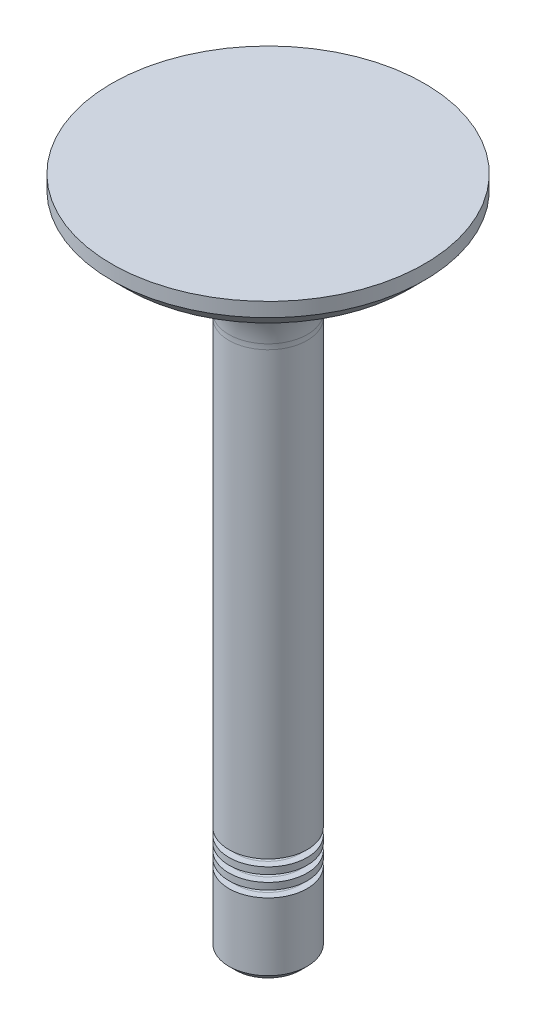
SolidWorks part; units mm, degrees
material "21-2N"
ref_plane "Front Plane" through (0, 0, 0) normal (0, 0, 1) x (1, 0, 0)
ref_plane "Top Plane" through (0, 0, 0) normal (0, 1, 0) x (1, 0, 0)
ref_plane "Right Plane" through (0, 0, 0) normal (1, 0, 0) x (0, 0, -1)
sketch "Sketch1" plane through (0, 0, 0) normal (0, 0, 1) x (1, 0, 0)
  line L0 (0, 105.7218) -> (0, 5.7218) construction
  line L1 (0, 105.7218) -> (-23.22, 105.7218)
  line L2 (-23.22, 105.7218) -> (-23.22, 103.6218)
  line L3 (-23.22, 103.6218) -> (-20.898, 101.2998)
  line L4 (0, 105.7218) -> (0, 5.7218)
  line L5 (-5.805, 87.4698) -> (-5.805, 5.7218)
  line L6 (-5.805, 5.7218) -> (0, 5.7218)
  arc A0 (-20.898, 101.2998) -> (-5.805, 87.4698) centre (-20.2665, 86.8383) cw
  dimension "D2" = 23.22
  dimension "D3" = 2.1
  dimension "D4" = 45
  dimension "D1" = 5.805
  dimension "D6" = 100
  dimension "D5" = 2.322
  dimension "D8" = 16.152
revolve "Revolve1" add sketch "Sketch1" angle 360 about L0
fillet "Fillet1" radius 10 1 edges at (-5.805, 87.4698, 0)
chamfer "Chamfer1" distance 1 angle 45 1 edges at (-5.805, 5.7218, 0)
sketch "Sketch2" plane through (0, 0, 0) normal (1, 0, 0) x (0, 0, -1)
  line L2 (-6.805, 19.7218) -> (-4.805, 19.7218)
  line L3 (-6.805, 18.7218) -> (-4.805, 18.7218)
  line L4 (0, 6.7218) -> (0, 87.9734) construction
  line L5 (5.805, 6.7218) -> (-5.805, 6.7218) construction
  line L6 (5.8358, 87.9734) -> (-5.8358, 87.9734) construction
  line L7 (-6.805, 18.7218) -> (-6.805, 19.7218)
  line L8 (-6.805, 16.7218) -> (-4.805, 16.7218)
  line L9 (-6.805, 16.7218) -> (-6.805, 17.7218)
  line L10 (-6.805, 17.7218) -> (-4.805, 17.7218)
  line L12 (-6.805, 21.7218) -> (-4.805, 21.7218)
  line L13 (-6.805, 20.7218) -> (-4.805, 20.7218)
  line L14 (-6.805, 20.7218) -> (-6.805, 21.7218)
  arc A1 (-4.805, 16.7218) -> (-4.805, 17.7218) centre (-4.805, 17.2218) ccw
  arc A2 (-4.805, 18.7218) -> (-4.805, 19.7218) centre (-4.805, 19.2218) ccw
  arc A3 (-4.805, 20.7218) -> (-4.805, 21.7218) centre (-4.805, 21.2218) ccw
  point P10 (-5.805, 17.2218)
  dimension "D1" = 10
  dimension "D2" = 1
  dimension "D3" = 3
revolve "Cut-Revolve1" cut sketch "Sketch2" angle 360 about L4
sketch "Sketch3" plane through (0, 0, 0) normal (0, 0, 1) x (1, 0, 0)
  line L0 (0, 105.7218) -> (0, -4.6075) construction
  line L1 (23.22, 105.7218) -> (-23.22, 105.7218) construction
equation "\"Valve Diameter\"= 46.44mm"
equation "\"Seat Angle Beta\"= 45deg"
equation "\"Seat Diameter\"= 41.796mm"
equation "\"Stem Diameter\"= 11.61mm"
equation "\"Seat Width\"= 2.322mm"
equation "\"Max Lift\"= 16.152mm"
equation "\"Overall Length\"= 100mm"
equation "\"Head Thickness\"= 2.1mm"
equation "\"D2@Sketch1\"=\"Valve Diameter\"/2"
equation "\"D3@Sketch1\"=\"Head Thickness\""
equation "\"D4@Sketch1\"=\"Seat Angle Beta\""
equation "\"D1@Sketch1\"=\"Stem Diameter\"/2"
equation "\"D6@Sketch1\"=\"Overall Length\""
equation "\"D5@Sketch1\"=\"Seat Width\""
equation "\"D8@Sketch1\"=\"Max Lift\""
